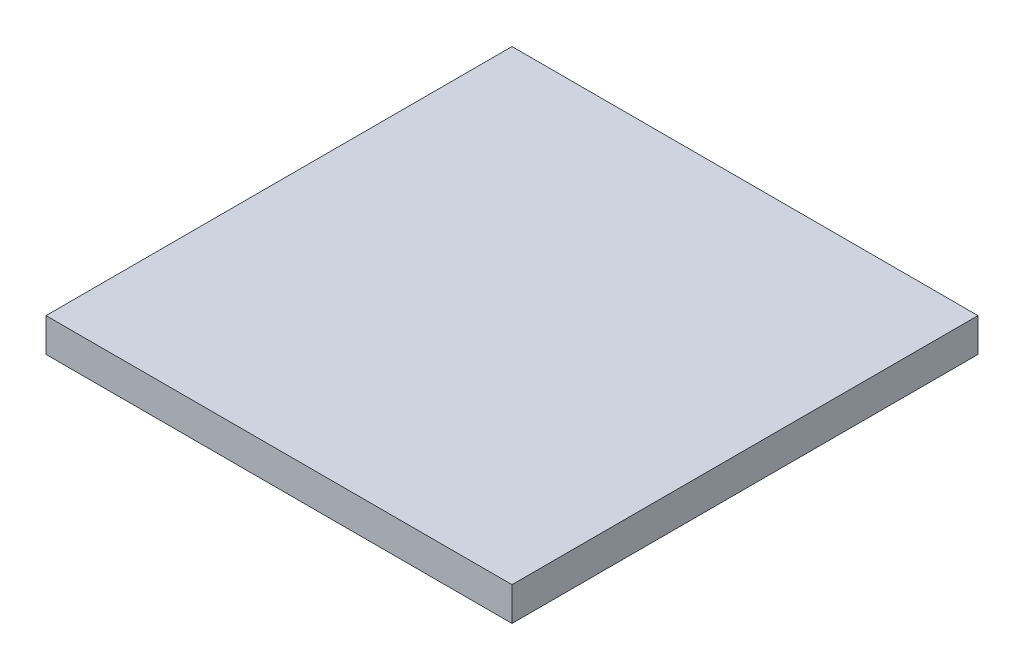
SolidWorks part; units mm, degrees
note: '?' marks a value the reader was unsure of. The reader was unsure of these and kept them because the rebuilt part matched: shared geometry of "Sketch1<3>", "Sketch1<4>", "Sketch2<3>".
other "DetailItem1" parameters "D4"=14.9454, "D7"=10.2919, "D11"=15, "D13"=13.4258, "D1"=140.0753, "D2"=179.4479, "D3"=12.9406, "D5"=11, "D6"=192, "D8"=36.2941, "D9"=10.4807, "D10"=125, "D12"=102.0515
material "ABS PC"
ref_plane "Front Plane" through (0, 0, 0) normal (0, 0, 1) x (1, 0, 0)
ref_plane "Top Plane" through (0, 0, 0) normal (0, 1, 0) x (1, 0, 0)
ref_plane "Right Plane" through (0, 0, 0) normal (1, 0, 0) x (0, 0, -1)
sketch "Sketch1" plane through (0, 0, 0) normal (0, 1, 0) x (1, 0, 0)
  line L0 (85, 96) -> (85, -96) construction
  line L1 (-96, 96) -> (96, 96)
  line L2 (-96, 96) -> (-96, -96)
  line L3 (-96, -96) -> (96, -96)
  line L4 (96, 96) -> (96, -96)
  line L5 (-96, 96) -> (96, -96) construction
  line L6 (-96, -96) -> (96, 96) construction
  line L7 (12, 96) -> (12, 85) construction
  line L8 (85, 0) -> (96, 0) construction
  line L9 (-65, 11.25) -> (-5, 11.25)
  line L11 (-80, 26.25) -> (-80, 65)
  line L12 (-65, 80) -> (65, 80)
  line L13 (80, 26.25) -> (80, 65)
  line L14 (-76.9571, -76.9571) -> (80, 80) construction
  line L15 (-80, 80) -> (79.6395, -79.6395) construction
  line L16 (5, 11.25) -> (65, 11.25)
  line L17 (0, 0) -> (0, 11.25) construction
  line L18 (5, 11.25) -> (0, 11.25) construction
  circle A0 centre (12, 85) radius 1.5
  circle A1 centre (85, 73) radius 1.5
  circle A2 centre (85, 0) radius 1.5
  circle A3 centre (85, -73) radius 1.5
  circle A4 centre (62.5, -87.5) radius 1.5
  arc A5 (-65, 11.25) -> (-80, 26.25) centre (-65, 26.25) cw
  arc A6 (65, 11.25) -> (80, 26.25) centre (65, 26.25) ccw
  arc A7 (65, 80) -> (80, 65) centre (65, 65) cw
  arc A8 (-80, 65) -> (-65, 80) centre (-65, 65) cw
  arc A9 (5, 11.25) -> (-5, 11.25) centre (0, 11.25) ccw
  point P0 (0, 0)
  point P20 (0, 0)
  dimension "D4" = 3
  dimension "D7" = 3
  dimension "D13" = 10
  dimension "D1" = 192
  dimension "D2" = 11
  dimension "D3" = 11
  dimension "D5" = 84
  dimension "D6" = 23
  dimension "D8" = 33.5
  dimension "D9" = 8.5
  dimension "D10" = 16
  dimension "D12" = 11.25
extrude "Boss-Extrude1" add sketch "Sketch1" along normal blind 13.85 contours A9 L16 A6 L13 A7 L12 A8 L11 A5 L9 | L4 L1 L2 L3 A4 A0 A1 A2 A3 L16 A9 L9 A5 L11 A8 L12 A7 L13 A6 | A4 | A3 | A2 | A1 | A0
extrude "Cut-Extrude1" cut sketch "Sketch1<3>" along normal offset from surface (11.85 mm away) 2 contours A9 L16 A6 L13 A7 L12 A8 L11 A5 L9 | A3 | A1 | A0 | A2 up to face at (0, 13.85, 0)
sketch "Sketch1<3>" plane through (0, 0, 0) normal (0, 1, 0) x (1, 0, 0) same geometry as "Sketch1"
extrude "Boss-Extrude2" add sketch "Sketch1<4>" against normal blind 3.5 contours A4
sketch "Sketch1<4>" plane through (0, 0, 0) normal (0, 1, 0) x (1, 0, 0) same geometry as "Sketch1"
ref_axis "Axis1" through (0, -0.6925, 0) along (0, 1, 0)?
pattern_circular "CirPattern1" count 2 over 360 about axis through (0, 0, 0) along (0, 1, 0) of "Cut-Extrude1", "Boss-Extrude2"
sketch "Sketch2" plane through (0, 13.85, 0) normal (0, 1, 0) x (1, 0, 0)
  line L0 (96, 96) -> (96, -96) construction
  line L1 (61.5, 66) -> (52.75, 66)
  line L2 (61.5, 66) -> (61.5, 38.2)
  line L3 (61.5, 38.2) -> (52.75, 38.2)
  line L4 (52.75, 66) -> (52.75, 38.2)
  line L5 (-96, 96) -> (96, 96) construction
  line L6 (-51.5, 66) -> (-51.5, 38.2)
  line L7 (-51.5, 66) -> (-60.25, 66)
  line L8 (-60.25, 66) -> (-60.25, 38.2)
  line L9 (-51.5, 38.2) -> (-60.25, 38.2)
  line L11 (-11, 56) -> (-19.75, 56)
  line L12 (-11, 56) -> (-11, 40)
  line L13 (-11, 40) -> (-19.75, 40)
  line L14 (-19.75, 56) -> (-19.75, 40)
  line L15 (29, 49) -> (-31, 49) construction
  line L16 (29, 49) -> (29, -47) construction
  line L17 (29, -47) -> (-31, -47) construction
  line L18 (-31, 49) -> (-31, -47) construction
  circle A0 centre (29, 49) radius 3.5
  circle A1 centre (-31, 49) radius 3.5
  circle A2 centre (-31, -47) radius 3.5
  circle A3 centre (29, -47) radius 3.5
  point P8 (58, 60.5)
  dimension "D13" = 7
  dimension "D1" = 34.5
  dimension "D2" = 30
  dimension "D3" = 27.8
  dimension "D4" = 8.75
  dimension "D5" = 35.5
  dimension "D6" = 38
  dimension "D8" = 113
  dimension "D9" = 8.75
  dimension "D10" = 16
  dimension "D11" = 40
  dimension "D12" = 107
  dimension "D14" = 60
  dimension "D15" = 96
  dimension "D16" = 67
  dimension "D17" = 47
  dimension "D7" = 2
extrude "Boss-Extrude4" add sketch "Sketch2" against normal blind 9.5 from surface at -2 contours L1 L4 L3 L2 | L11 L14 L13 L12 | L9 L6 L7 L8 starting at face at (0, 11.85, -39.25)
extrude "Boss-Extrude5" add sketch "Sketch2<3>" against normal blind 5.5 from surface at -2 contours A0 | A1 | A3 | A2 starting at face at (-55.875, 11.85, -52.1)
sketch "Sketch2<3>" plane through (0, 13.85, 0) normal (0, 1, 0) x (1, 0, 0) same geometry as "Sketch2"
sketch "Sketch3" plane through (0, 0, 0) normal (0, 1, 0) x (1, 0, 0)
  line L0 (-60.25, 66) -> (-51.5, 66) construction
  line L1 (-51.5, 66) -> (-51.5, 38.2) construction
  line L2 (-51.5, 38.2) -> (-60.25, 38.2) construction
  line L3 (-60.25, 38.2) -> (-60.25, 66) construction
  line L4 (-11, 40) -> (-19.75, 40) construction
  line L5 (-19.75, 40) -> (-19.75, 56) construction
  line L6 (-19.75, 56) -> (-11, 56) construction
  line L7 (-11, 56) -> (-11, 40) construction
  line L8 (61.5, 38.2) -> (52.75, 38.2) construction
  line L9 (52.75, 38.2) -> (52.75, 66) construction
  line L10 (52.75, 66) -> (61.5, 66) construction
  line L11 (61.5, 66) -> (61.5, 38.2) construction
  line L12 (96, 96) -> (96, -96) construction
  line L13 (96, -96) -> (-96, -96) construction
  line L14 (-96, -96) -> (-96, 96) construction
  line L15 (-96, 96) -> (96, 96) construction
  line L16 (-60.25, 66) -> (-51.5, 66)
  line L17 (-51.5, 66) -> (-51.5, 38.2)
  line L18 (-51.5, 38.2) -> (-60.25, 38.2)
  line L19 (-60.25, 38.2) -> (-60.25, 66)
  line L20 (-11, 40) -> (-19.75, 40)
  line L21 (-19.75, 40) -> (-19.75, 56)
  line L22 (-19.75, 56) -> (-11, 56)
  line L23 (-11, 56) -> (-11, 40)
  line L24 (61.5, 38.2) -> (52.75, 38.2)
  line L25 (52.75, 38.2) -> (52.75, 66)
  line L26 (52.75, 66) -> (61.5, 66)
  line L27 (61.5, 66) -> (61.5, 38.2)
  line L28 (96, 96) -> (96, -96)
  line L29 (96, -96) -> (-96, -96)
  line L30 (-96, -96) -> (-96, 96)
  line L31 (-96, 96) -> (96, 96)
  line L32 (80, -26.25) -> (80, -65) construction
  line L33 (65, -80) -> (-65, -80) construction
  line L34 (-80, -26.25) -> (-80, -65) construction
  line L35 (-5, -11.25) -> (-65, -11.25) construction
  line L36 (65, -11.25) -> (5, -11.25) construction
  line L37 (80, 26.25) -> (80, 65) construction
  line L38 (5, 11.25) -> (65, 11.25) construction
  line L39 (-65, 11.25) -> (-5, 11.25) construction
  line L40 (-80, 26.25) -> (-80, 65) construction
  line L41 (-65, 80) -> (65, 80) construction
  line L42 (80, -26.25) -> (80, -65)
  line L43 (65, -80) -> (-65, -80)
  line L44 (-80, -26.25) -> (-80, -65)
  line L45 (-5, -11.25) -> (-65, -11.25)
  line L46 (65, -11.25) -> (5, -11.25)
  line L47 (80, 26.25) -> (80, 65)
  line L48 (5, 11.25) -> (65, 11.25)
  line L49 (-65, 11.25) -> (-5, 11.25)
  line L50 (-80, 26.25) -> (-80, 65)
  line L51 (-65, 80) -> (65, 80)
  circle A0 centre (29, -47) radius 3.5 construction
  circle A1 centre (-31, -47) radius 3.5 construction
  circle A2 centre (-31, 49) radius 3.5 construction
  circle A3 centre (29, 49) radius 3.5 construction
  circle A4 centre (29, -47) radius 3.5
  circle A5 centre (-31, -47) radius 3.5
  circle A6 centre (-31, 49) radius 3.5
  circle A7 centre (29, 49) radius 3.5
  arc A8 (65, -80) -> (80, -65) centre (65, -65) ccw construction
  arc A9 (-80, -65) -> (-65, -80) centre (-65, -65) ccw construction
  arc A10 (-65, -11.25) -> (-80, -26.25) centre (-65, -26.25) ccw construction
  arc A11 (-5, -11.25) -> (5, -11.25) centre (0, -11.25) ccw construction
  arc A12 (80, -26.25) -> (65, -11.25) centre (65, -26.25) ccw construction
  arc A13 (65, 11.25) -> (80, 26.25) centre (65, 26.25) ccw construction
  arc A14 (5, 11.25) -> (-5, 11.25) centre (0, 11.25) ccw construction
  arc A15 (-80, 26.25) -> (-65, 11.25) centre (-65, 26.25) ccw construction
  arc A16 (-65, 80) -> (-80, 65) centre (-65, 65) ccw construction
  arc A17 (80, 65) -> (65, 80) centre (65, 65) ccw construction
  arc A18 (65, -80) -> (80, -65) centre (65, -65) ccw
  arc A19 (-80, -65) -> (-65, -80) centre (-65, -65) ccw
  arc A20 (-65, -11.25) -> (-80, -26.25) centre (-65, -26.25) ccw
  arc A21 (-5, -11.25) -> (5, -11.25) centre (0, -11.25) ccw
  arc A22 (80, -26.25) -> (65, -11.25) centre (65, -26.25) ccw
  arc A23 (65, 11.25) -> (80, 26.25) centre (65, 26.25) ccw
  arc A24 (5, 11.25) -> (-5, 11.25) centre (0, 11.25) ccw
  arc A25 (-80, 26.25) -> (-65, 11.25) centre (-65, 26.25) ccw
  arc A26 (-65, 80) -> (-80, 65) centre (-65, 65) ccw
  arc A27 (80, 65) -> (65, 80) centre (65, 65) ccw
  circle A28 centre (85, 0) radius 1.5 construction
  circle A29 centre (85, -73) radius 1.5 construction
  circle A30 centre (62.5, -87.5) radius 1.5 construction
  circle A31 centre (-12, -85) radius 1.5 construction
  circle A32 centre (-85, -73) radius 1.5 construction
  circle A33 centre (-85, 0) radius 1.5 construction
  circle A34 centre (-85, 73) radius 1.5 construction
  circle A35 centre (-62.5, 87.5) radius 1.5 construction
  circle A36 centre (12, 85) radius 1.5 construction
  circle A37 centre (85, 73) radius 1.5 construction
  circle A38 centre (85, 0) radius 1.5
  circle A39 centre (85, -73) radius 1.5
  circle A40 centre (62.5, -87.5) radius 1.5
  circle A41 centre (-12, -85) radius 1.5
  circle A42 centre (-85, -73) radius 1.5
  circle A43 centre (-85, 0) radius 1.5
  circle A44 centre (-85, 73) radius 1.5
  circle A45 centre (-62.5, 87.5) radius 1.5
  circle A46 centre (12, 85) radius 1.5
  circle A47 centre (85, 73) radius 1.5
